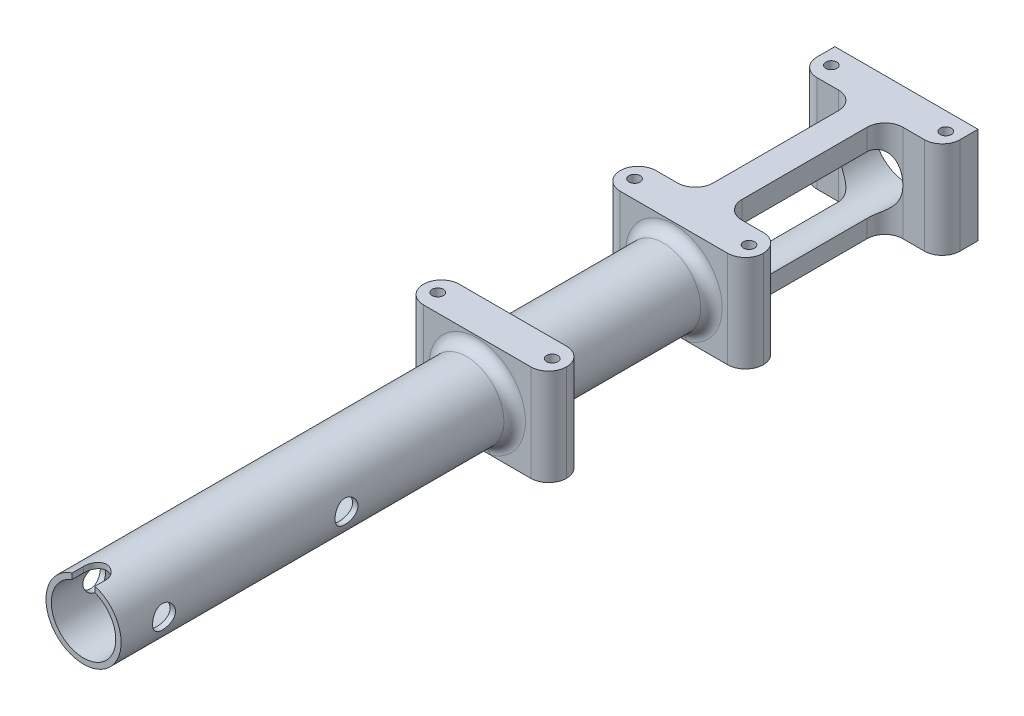
SolidWorks part; units mm, degrees
material "6063-T6"
ref_plane "Front Plane" through (0, 0, 0) normal (0, 0, 1) x (1, 0, 0)
ref_plane "Top Plane" through (0, 0, 0) normal (0, 1, 0) x (1, 0, 0)
ref_plane "Right Plane" through (0, 0, 0) normal (1, 0, 0) x (0, 0, -1)
sketch "Sketch1" plane through (0, 0, 0) normal (0, 0, 1) x (1, 0, 0)
  circle A1 centre (0, 0) radius 10.5
  dimension "D1" = 21
extrude "Boss-Extrude1" add sketch "Sketch1" along normal blind 165
sketch "Sketch3" plane through (0, 0, 0) normal (0, 1, 0) x (1, 0, 0)
  line L0 (0, 0) -> (0, 101.6874) construction
  line L1 (0, 0) -> (-109.3194, 0) construction
  line L2 (20, 0) -> (-20, 0)
  line L3 (-20, 0) -> (-20, 10)
  line L4 (-20, 10) -> (-4, 10)
  line L5 (-4, 10) -> (-4, 55)
  line L6 (-4, 55) -> (-20, 55)
  line L7 (-20, 55) -> (-20, 65)
  line L8 (-20, 65) -> (20, 65)
  line L9 (20, 55) -> (20, 65)
  line L10 (4, 55) -> (20, 55)
  line L11 (4, 10) -> (4, 55)
  line L12 (20, 10) -> (4, 10)
  line L13 (20, 0) -> (20, 10)
  line L14 (-20, 5) -> (36.7917, 5) construction
  line L15 (-20, 60) -> (21.8388, 60) construction
  line L17 (12, -45) -> (-20, -45) construction
  line L24 (0, -50.1148) -> (0, -24.3835) construction
  line L28 (-20, -55) -> (20, -55)
  line L29 (-20, -55) -> (-20, -45)
  line L30 (-20, -45) -> (20, -45)
  line L31 (20, -55) -> (20, -45)
  line L32 (-20, -55) -> (20, -45) construction
  line L33 (-20, -45) -> (20, -55) construction
  circle A0 centre (-16, 5) radius 1.55
  circle A1 centre (16, 5) radius 1.55
  circle A4 centre (-16, 60) radius 1.55
  circle A5 centre (16, 60) radius 1.55
  circle A6 centre (16, -50) radius 1.55
  circle A7 centre (-16, -50) radius 1.55
  point P12 (0, 65)
  point P29 (0, -36.7499)
  point P30 (0, -36.7499)
  point P33 (0, -40.32)
  dimension "D6" = 3.1
  dimension "D8" = 3.1
  dimension "D11" = 32
  dimension "D12" = 55
  dimension "D13" = 32
  dimension "D2" = 45
  dimension "D3" = 10
  dimension "D4" = 10
  dimension "D5" = 8
  dimension "D7" = 4
  dimension "D9" = 5
  dimension "D10" = 40
  dimension "D14" = 40
  dimension "D15" = 45
  dimension "D16" = 10
  dimension "D17" = 40
extrude "Boss-Extrude2" add sketch "Sketch3" along normal blind 14 and the other way blind 13
sketch "Sketch6" plane through (0, 0, 0) normal (0, 0, 1) x (1, 0, 0)
  circle A0 centre (0, 0) radius 9
  dimension "D1" = 18
extrude "Cut-Extrude1" cut sketch "Sketch6" against normal through all both and the other way through all
sketch "Sketch7" plane through (0, 0, 0) normal (1, 0, 0) x (0, 0, -1)
  line L0 (-165, 9) -> (-165, -9) construction
  circle A0 centre (-102, 0) radius 3.2
  circle A1 centre (-153, 0) radius 3.2
  dimension "D1" = 6.4
  dimension "D2" = 12
  dimension "D3" = 63
extrude "Cut-Extrude2" cut sketch "Sketch7" against normal through all both and the other way through all
sketch "Sketch8" plane through (0, 0, 0) normal (0, 1, 0) x (1, 0, 0)
  line L0 (0, 0) -> (0, -186.8535) construction
  line L1 (3.2, -165) -> (-3.2, -165)
  line L2 (-3.2, -165) -> (-3.2, -161.8)
  line L3 (3.2, -165) -> (3.2, -161.8)
  line L4 (-10.5, -165) -> (10.5, -165) construction
  arc A0 (-3.2, -161.8) -> (3.2, -161.8) centre (0, -161.8) cw
  point P9 (0, -165)
  dimension "D1" = 3.2
  dimension "D2" = 3.2
extrude "Cut-Extrude3" cut sketch "Sketch8" along normal through all
fillet "Fillet1" radius 5 14 edges at (-4, 11.0311, -55) (4, 11.0311, -55) (-4, 11.0311, -10) (4, 11.0311, -10) (-4, -10.5311, -55) (4, -10.5311, -55) (4, -10.5311, -10) (-4, -10.5311, -10) (-20, 0.5, -10) (-20, 0.5, 0) (-20, 0.5, -55) (20, 0.5, -55) (20, 0.5, -10) (20, 0.5, 0)
fillet "Fillet3" radius 3 1 edges at (10.5, 0, 0)
fillet "圆角1" radius 5 4 edges at (20, 0.5, 55) (20, 0.5, 45) (-20, 0.5, 55) (-20, 0.5, 45)
fillet "圆角2" radius 3 2 edges at (10.5, 0, 55) (-10.5, 0, 45)
